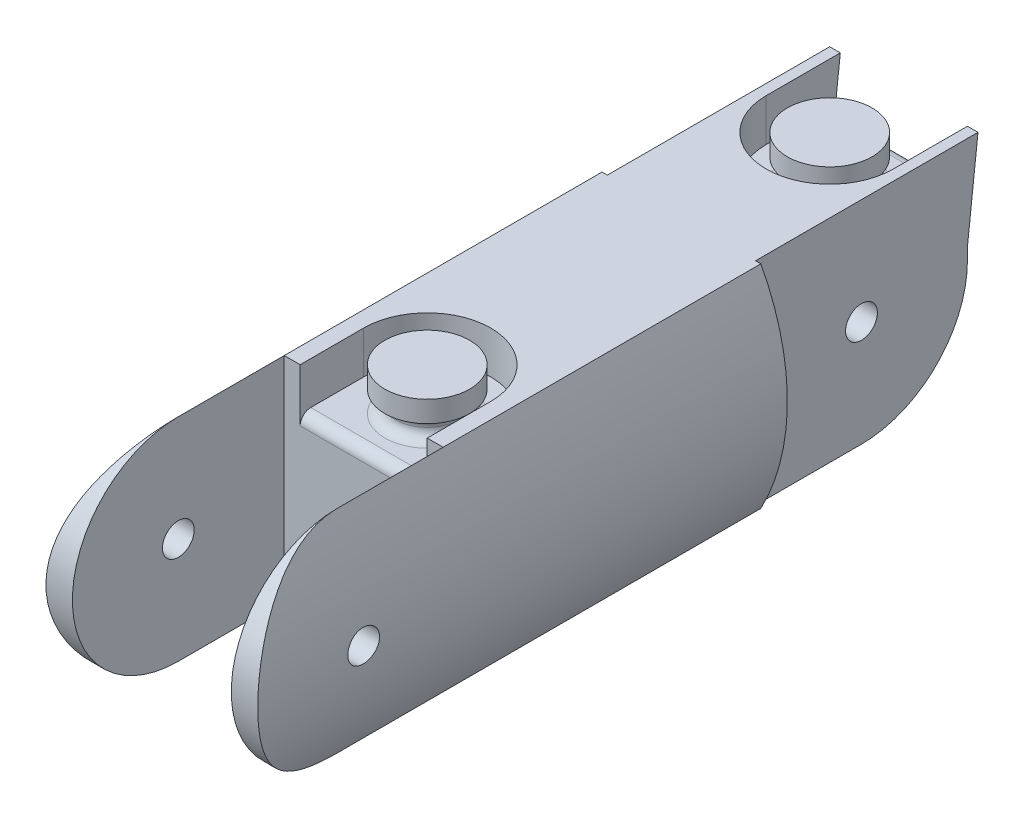
SolidWorks part; units mm, degrees
ref_plane "Alzado" through (0, 0, 0) normal (0, 0, 1) x (1, 0, 0)
ref_plane "Planta" through (0, 0, 0) normal (0, 1, 0) x (1, 0, 0)
ref_plane "Vista lateral" through (0, 0, 0) normal (1, 0, 0) x (0, 0, -1)
sketch "Croquis2" plane through (0, 0, 0) normal (0, 0, 1) x (1, 0, 0)
  line L5 (-7.5, -10) -> (7.5, -10)
  line L7 (-7.5, 10) -> (7.5, 10)
  line L9 (-7.5, -10) -> (7.5, 10) construction
  line L10 (-7.5, 10) -> (7.5, -10) construction
  arc A2 (-7.5, 10) -> (-7.5, -10) centre (11.25, 0) ccw
  arc A3 (7.5, -10) -> (7.5, 10) centre (-11.25, 0) ccw
  point P0 (0, 0)
  dimension "D1" = 15
  dimension "D2" = 20
extrude "Saliente-Extruir2" add sketch "Croquis2" along normal blind 50
sketch "Croquis4" plane through (0, 0, 0) normal (0, 0, -1) x (-1, 0, 0)
  line L1 (7.5, -10) -> (-7.5, -10) construction
  circle A0 centre (0, -7) radius 1.5
  dimension "D2" = 3
  dimension "D1" = 3
extrude "Cortar-Extruir1" cut sketch "Croquis4" against normal blind 50
sketch "Croquis3" plane through (0, 0, 0) normal (0, 0, -1) x (-1, 0, 0)
  line L8 (7.5, -10) -> (-7.5, -10) construction
  line L10 (7, 10) -> (7, -10)
  line L11 (7, -10) -> (3, -10)
  line L12 (-7, 10) -> (-7, -10)
  line L13 (7, 10) -> (-7, -10) construction
  line L14 (7, -10) -> (-7, 10) construction
  line L17 (-3, -10) -> (-7, -10)
  line L19 (-3, -3) -> (3, -3)
  line L20 (-3, -3) -> (-3, -10)
  line L21 (3, -3) -> (3, -10)
  line L22 (-7, 10) -> (7, 10)
  point P0 (0, 0)
  dimension "D1" = 14
  dimension "D2" = 4
  dimension "D3" = 4
  dimension "D4" = 7
extrude "Saliente-Extruir3" add sketch "Croquis3" along normal blind 20
sketch "Croquis8" plane through (-7, 0, 0) normal (-1, 0, 0) x (0, 0, 1)
  line L0 (-20, -10) -> (-20, 10) construction
  line L1 (-20, -10) -> (0, -10) construction
  circle A0 centre (-10, 0) radius 1.5
  point P4 (-20, 0)
  dimension "D1" = 3
  dimension "D2" = 10
  dimension "D3" = 10
extrude "Cortar-Extruir4" cut sketch "Croquis8" against normal blind 14
fillet "Redondeo1" radius 10 2 edges at (-5, -10, -20) (5, -10, -20)
sketch "Croquis6" plane through (0, 0, 50) normal (0, 0, 1) x (1, 0, 0)
  line L1 (-7.5, 10) -> (7.5, 10)
  line L2 (-7.5, 10) -> (-7.5, -10)
  line L3 (-7.5, -10) -> (7.5, -10)
  line L4 (7.5, 10) -> (7.5, -10)
extrude "Cortar-Extruir2" cut sketch "Croquis6" against normal blind 20
sketch "Croquis7" plane through (0, 0, 0) normal (1, 0, 0) x (0, 0, -1)
  line L0 (-50, 10) -> (-50, -10) construction
  line L2 (-40, -10) -> (-55, -10)
  line L4 (-40, 10) -> (-55, 10)
  line L5 (-55, -10) -> (-55, 10)
  arc A0 (-40, 10) -> (-40, -10) centre (-40, 0) ccw
  circle A1 centre (-40, 0) radius 1.5
  dimension "D3" = 10
  dimension "D4" = 3
  dimension "D1" = 10
  dimension "D2" = 15
  dimension "D5" = 20
extrude "Cortar-Extruir3" cut sketch "Croquis7" against normal through all both and the other way through all
sketch "Sketch1" plane through (0, 10, 0) normal (0, 1, 0) x (1, 0, 0)
  line L0 (-7, 20) -> (7, 20) construction
  line L1 (7.5, -30) -> (-7.5, -30) construction
  line L4 (-6, -24) -> (-6, -30)
  line L5 (-6, -30) -> (6, -30)
  line L6 (6, -24) -> (6, -30)
  line L8 (-6, 14) -> (-6, 20)
  line L9 (-6, 20) -> (6, 20)
  line L10 (6, 14) -> (6, 20)
  arc A0 (6, -24) -> (-6, -24) centre (0, -24) ccw
  arc A1 (-6, 14) -> (6, 14) centre (0, 14) ccw
  dimension "D2" = 12
  dimension "D4" = 12
  dimension "D1" = 6
  dimension "D3" = 6
extrude "Cut-Extrude1" cut sketch "Sketch1" against normal blind 4
sketch "Sketch2" plane through (0, 6, 0) normal (0, 1, 0) x (1, 0, 0)
  circle A0 centre (0, -24) radius 3
  circle A1 centre (0, 14) radius 3
  dimension "D1" = 6
  dimension "D2" = 6
extrude "Boss-Extrude1" add sketch "Sketch2" along normal blind 2
sketch "Sketch3" plane through (0, 8, 0) normal (0, 1, 0) x (1, 0, 0)
  circle A0 centre (0, -24) radius 4
  circle A1 centre (0, 14) radius 4
  dimension "D1" = 8
  dimension "D2" = 8
extrude "Boss-Extrude2" add sketch "Sketch3" along normal blind 2
fillet "Fillet2" radius 1 4 edges at (0, 8, -11) (0, 6, -11) (0, 8, 27) (0, 6, 27)
fillet "Fillet3" radius 1 2 edges at (0, 6, -20) (0, 6, 30)
fillet "Fillet4" radius 1 2 edges at (-1.5, -7, 0) (1.5, -7, 30)
sketch "Sketch4" plane through (7, 0, 0) normal (1, 0, 0) x (0, 0, -1)
  line L0 (20, 10) -> (21, 10)
  line L1 (21, 10) -> (19.5394, -3)
  line L2 (19.5394, -3) -> (20, 10)
  dimension "D1" = 1
sketch "Sketch5" plane through (-7, 0, 0) normal (-1, 0, 0) x (0, 0, 1)
  line L0 (-20, 10) -> (-21, 10)
  line L1 (-21, 10) -> (-19.5394, -3)
  line L2 (-19.5394, -3) -> (-20, 10)
extrude "Boss-Extrude3" add sketch "Sketch4" against normal blind 1
extrude "Boss-Extrude4" add sketch "Sketch5" against normal blind 1
